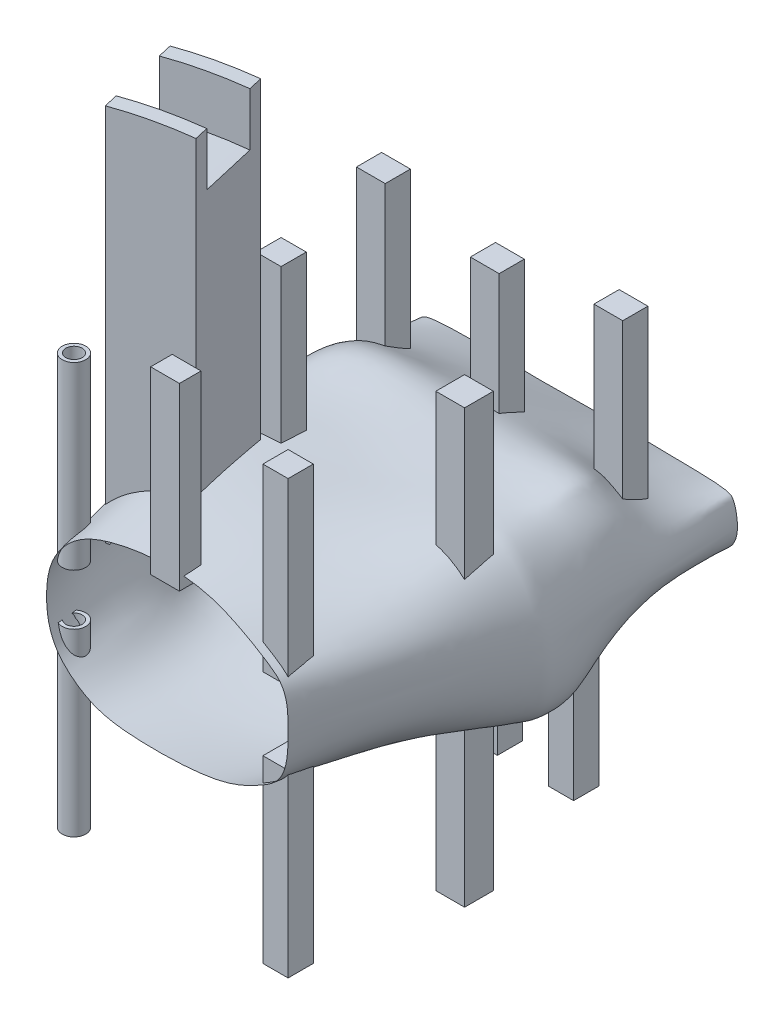
SolidWorks part; units mm, degrees
ref_plane "Front Plane" through (0, 0, 0) normal (0, 0, 1) x (1, 0, 0)
ref_plane "Top Plane" through (0, 0, 0) normal (0, 1, 0) x (1, 0, 0)
ref_plane "Right Plane" through (0, 0, 0) normal (1, 0, 0) x (0, 0, -1)
sketch "Sketch1" plane through (0, 8, 0) normal (0, 1, 0) x (1, 0, 0)
  line L1 (-4, -2.5) -> (4, -2.5)
  line L2 (-4, -2.5) -> (-4, -9.5)
  line L3 (-4, -9.5) -> (4, -9.5)
  line L4 (4, -2.5) -> (4, -9.5)
  line L5 (62, -2.5) -> (70, -2.5)
  line L6 (62, -2.5) -> (62, -9.5)
  line L7 (62, -9.5) -> (70, -9.5)
  line L8 (70, -2.5) -> (70, -9.5)
extrude "Boss-Extrude1" add sketch "Sketch1" along normal blind 50 from offset 0.1
sketch "Sketch2" plane through (0, 4, 0) normal (0, 1, 0) x (1, 0, 0)
  line L10 (37.5, -11.35) -> (37.5, -4.35)
  line L11 (37.5, -4.35) -> (29.5, -4.35)
  line L12 (29.5, -4.35) -> (29.5, -11.35)
  line L13 (29.5, -11.35) -> (33.75, -11.35)
  line L14 (33.75, -11.35) -> (37.5, -11.35)
  line L15 (37.5, -11.35) -> (37.5, -4.35)
  line L16 (37.5, -4.35) -> (29.5, -4.35)
  line L17 (29.5, -4.35) -> (29.5, -11.35)
  line L18 (29.5, -11.35) -> (33.75, -11.35)
  line L19 (33.75, -11.35) -> (37.5, -11.35)
  dimension "D1" = 0.2
extrude "Boss-Extrude2" add sketch "Sketch2" along normal blind 50 from offset 0.1 separate body
sketch "Sketch3" plane through (0, 9, 0) normal (0, 1, 0) x (1, 0, 0)
  line L1 (-9.75, -44.95) -> (-2.75, -44.95)
  line L2 (-9.75, -44.95) -> (-9.75, -51.95)
  line L3 (-9.75, -51.95) -> (-2.75, -51.95)
  line L4 (-2.75, -44.95) -> (-2.75, -51.95)
extrude "Boss-Extrude3" add sketch "Sketch3" along normal blind 50 from offset 0.1 separate body
sketch "Sketch4" plane through (0, 16, 0) normal (0, 1, 0) x (1, 0, 0)
  line L4 (17.5, -51.95) -> (17.5, -44.95)
  line L5 (17.5, -44.95) -> (10.5, -44.95)
  line L6 (10.5, -44.95) -> (10.5, -51.95)
  line L7 (10.5, -51.95) -> (17.5, -51.95)
  line L8 (17.5, -51.95) -> (17.5, -44.95)
  line L9 (17.5, -44.95) -> (10.5, -44.95)
  line L10 (10.5, -44.95) -> (10.5, -51.95)
  line L11 (10.5, -51.95) -> (17.5, -51.95)
  dimension "D1" = 0
extrude "Boss-Extrude4" add sketch "Sketch4" along normal blind 50 from offset 0.1 separate body
sketch "Sketch5" plane through (0, 8, 0) normal (0, 1, 0) x (1, 0, 0)
  line L4 (61, -52.45) -> (69, -52.45)
  line L5 (69, -52.45) -> (69, -44.45)
  line L6 (69, -44.45) -> (61, -44.45)
  line L7 (61, -44.45) -> (61, -52.45)
  line L8 (61, -52.45) -> (69, -52.45)
  line L9 (69, -52.45) -> (69, -44.45)
  line L10 (69, -44.45) -> (61, -44.45)
  line L11 (61, -44.45) -> (61, -52.45)
  dimension "D1" = 0
extrude "Boss-Extrude5" add sketch "Sketch5" along normal blind 50 from offset 0.1 separate body
sketch "Sketch6" plane through (0, 9, 0) normal (0, 1, 0) x (1, 0, 0)
  line L4 (55.5, -95) -> (62.5, -95)
  line L5 (62.5, -95) -> (62.5, -88)
  line L6 (62.5, -88) -> (55.5, -88)
  line L7 (55.5, -88) -> (55.5, -95)
  line L8 (55.5, -95) -> (62.5, -95)
  line L9 (62.5, -95) -> (62.5, -88)
  line L10 (62.5, -88) -> (55.5, -88)
  line L11 (55.5, -88) -> (55.5, -95)
  dimension "D1" = 0
extrude "Boss-Extrude6" add sketch "Sketch6" along normal blind 50 from offset 0.1 separate body
sketch "Sketch7" plane through (0, 20, 0) normal (0, 1, 0) x (1, 0, 0)
  line L8 (35.5, -92.2) -> (27.5, -92.2)
  line L9 (27.5, -92.2) -> (27.5, -98.2)
  line L10 (27.5, -98.2) -> (35.5, -98.2)
  line L11 (35.5, -98.2) -> (35.5, -92.2)
  line L12 (35.5, -92.2) -> (27.5, -92.2)
  line L13 (27.5, -92.2) -> (27.5, -98.2)
  line L14 (27.5, -98.2) -> (35.5, -98.2)
  line L15 (35.5, -98.2) -> (35.5, -92.2)
  dimension "D1" = 0.2
extrude "Boss-Extrude7" add sketch "Sketch7" along normal blind 50 from offset 0.1 separate body
sketch "Sketch8" plane through (0, 6, 0) normal (0, 1, 0) x (1, 0, 0)
  circle A0 centre (-0.5, -91.5) radius 2.275
  circle A1 centre (-0.5, -91.5) radius 3.275
  arc A2 (-1.6902, -94.5511) -> (-1.0727, -88.2755) centre (-0.5, -91.5) ccw construction
  circle A3 centre (-0.5, -91.5) radius 2.275 construction
extrude "Boss-Extrude8" add sketch "Sketch8" along normal blind 50 from offset 0.1 separate body
sketch "Sketch9" plane through (0, -12, 0) normal (0, -1, 0) x (1, 0, 0)
  line L1 (7.5, 11.65) -> (14.5, 11.65)
  line L2 (7.5, 11.65) -> (7.5, 4.65)
  line L3 (7.5, 4.65) -> (14.5, 4.65)
  line L4 (14.5, 11.65) -> (14.5, 4.65)
  line L5 (30, 11.35) -> (37, 11.35)
  line L6 (30, 11.35) -> (30, 4.35)
  line L7 (30, 4.35) -> (37, 4.35)
  line L8 (37, 11.35) -> (37, 4.35)
  line L9 (58.5, 11.65) -> (51.5, 11.65)
  line L10 (58.5, 11.65) -> (58.5, 4.65)
  line L11 (58.5, 4.65) -> (51.5, 4.65)
  line L12 (51.5, 11.65) -> (51.5, 4.65)
  line L13 (61, 52.45) -> (69, 52.45)
  line L14 (61, 52.45) -> (61, 44.45)
  line L15 (61, 44.45) -> (69, 44.45)
  line L16 (69, 52.45) -> (69, 44.45)
extrude "Boss-Extrude9" add sketch "Sketch9" along normal blind 50 from offset 0.1 separate body
sketch "Sketch10" plane through (0, -11, 0) normal (0, -1, 0) x (1, 0, 0)
  line L1 (55.5, 95) -> (62.5, 95)
  line L2 (55.5, 95) -> (55.5, 88)
  line L3 (55.5, 88) -> (62.5, 88)
  line L4 (62.5, 95) -> (62.5, 88)
  line L5 (17.5, 51.95) -> (10.5, 51.95)
  line L6 (17.5, 51.95) -> (17.5, 44.95)
  line L7 (17.5, 44.95) -> (10.5, 44.95)
  line L8 (10.5, 51.95) -> (10.5, 44.95)
extrude "Boss-Extrude10" add sketch "Sketch10" along normal blind 50 from offset 0.1 separate body
sketch "Sketch11" plane through (0, -8, 0) normal (0, -1, 0) x (1, 0, 0)
  circle A0 centre (-0.5, 91.5) radius 2.275 construction
  circle A1 centre (-0.5, 91.5) radius 3.275
  circle A2 centre (-0.5, 91.5) radius 3.275
  circle A3 centre (-0.5, 91.5) radius 2.275
  dimension "D1" = 0
extrude "Boss-Extrude11" add sketch "Sketch11" along normal blind 50 from offset 0.1 separate body
ref_plane "Plane1" through (12.8977, 0, 55.8661) normal (0.225, 0, 0.9744) x (0.9744, 0, -0.225)
ref_plane "Plane2" through (15.1472, 0, 65.6098) normal (0.225, 0, 0.9744) x (0.9744, 0, -0.225)
sketch "Sketch12" plane through (12.8977, 0, 55.8661) normal (0.225, 0, 0.9744) x (0.9744, 0, -0.225)
  circle A0 centre (-9.3704, 0) radius 10.7
  dimension "D1" = 21.4
extrude "Extrude-Thin1" add sketch "Sketch12" along normal mid plane 4 separate body thin thin type one direction wall 100
sketch "Sketch13" plane through (13.3476, 0, 57.8148) normal (0.225, 0, 0.9744) x (0.9744, 0, -0.225)
  line L0 (0.0896, 5) -> (1.1296, 5)
  line L1 (1.1296, 5) -> (1.1296, 110.2009)
  line L2 (-19.8704, 110.2009) -> (-19.8704, 5)
  line L3 (-20.0704, 6) -> (-20.0704, 0) construction
  line L4 (1.3296, 6) -> (1.3296, 0) construction
  line L5 (-19.8704, 5) -> (-18.8303, 5)
  line L6 (-15.9888, 6) -> (-22.9251, 6) construction
  circle A0 centre (-9.3704, 0) radius 10.7 construction
  circle A1 centre (-9.3704, 0) radius 110.7 construction
  arc A2 (-19.8704, 110.2009) -> (1.1296, 110.2009) centre (-9.3704, 0) ccw
  arc A3 (0.0896, 5) -> (-18.8303, 5) centre (-9.3704, 0) ccw
  dimension "D1" = 0.2
  dimension "D2" = 0.2
  dimension "D3" = 1
extrude "Cut-Extrude1" cut sketch "Sketch13" against normal through all both and the other way through all
mirror "Mirror1" about plane through (15.1472, 0, 65.6098) normal (0.225, 0, 0.9744) of bodies 118
sketch "Sketch14" plane through (17.8466, 0, 77.3022) normal (0.225, 0, 0.9744) x (0.9744, 0, -0.225)
  circle A0 centre (-9.3704, 0) radius 16
  dimension "D1" = 32
extrude "Extrude-Thin2" add sketch "Sketch14" against normal up to surface (24 mm away) thin up to face at (3.3176, 41.1002, 56.0252) thin type one direction wall 80
extrude "Cut-Extrude2" cut sketch "Sketch13<3>" against normal through all both and the other way through all
sketch "Sketch13<3>" plane through (13.3476, 0, 57.8148) normal (0.225, 0, 0.9744) x (0.9744, 0, -0.225) same geometry as "Sketch13"
fillet "Fillet1" radius 0.5 2 edges at (16.2479, 12.0727, 65.3557) (-4.2139, 12.0727, 70.0796)
ref_plane "Plane3" through (0, 0, 0) normal (0, 1, 0) x (1, 0, 0)
sketch "Sketch15" plane through (0, 0, 0) normal (0, 1, 0) x (1, 0, 0)
  line L0 (-12.1525, 15) -> (-15.2953, -40.3087)
  line L1 (-15.0551, -43.1255) -> (-2.294, -98.4)
  line L2 (64.1595, -98.4) -> (79.2818, -41.9628)
  line L3 (79.614, -38.9613) -> (77.3822, 15)
  line L4 (76.3839, -33.4595) -> (75, 0) construction
  line L5 (76.7992, -43.5006) -> (63.0268, -94.9) construction
  line L6 (-12.3568, -41.4768) -> (-8.5998, -57.7502) construction
  line L7 (-10, 0) -> (-12.2621, -39.8092) construction
  line L9 (64.1595, -98.4) -> (65.0973, -94.9)
  line L10 (-2.294, -98.4) -> (-3.102, -94.9)
  line L12 (75, 0) -> (47, 0) construction
  arc A0 (79.2818, -41.9628) -> (79.614, -38.9613) centre (69.6226, -39.3746) ccw
  arc A1 (-15.2953, -40.3087) -> (-15.0551, -43.1255) centre (-5.3114, -40.876) ccw
  point P14 (0, 0)
  point P24 (0, 0)
  point P25 (63.9468, -99.1937)
  point P26 (0, 0)
  point P28 (0, 0)
  point P30 (0, 0)
  point P32 (0, 0)
  point P33 (-11.5291, 25.9717)
  point P34 (0, 0)
  point P35 (77.212, 19.1146)
  point P36 (77.0804, 22.2963)
  dimension "D5" = 10
  dimension "D1" = 3
  dimension "D2" = 2
  dimension "D3" = 3
  dimension "D4" = 3
  dimension "D6" = 15
ref_plane "Plane4" through (0, 0, -15) normal (0, 0, -1) x (-1, 0, 0)
ref_plane "Plane5" through (0, 0, 41.97) normal (0, 0, 1) x (1, 0, 0)
ref_plane "Plane6" through (0, 0, 29.03) normal (0, 0, -1) x (-1, 0, 0)
ref_plane "Plane7" through (0, 0, 67.45) normal (0, 0, 1) x (1, 0, 0)
ref_plane "Plane8" through (0, 0, 97) normal (0, 0, 1) x (1, 0, 0)
sketch "Sketch16" plane through (0, 0, -15) normal (0, 0, -1) x (-1, 0, 0)
  line L0 (-64.1595, 0) -> (-79.2818, 0) construction
  line L1 (-79.614, 0) -> (-77.3822, 0) construction
  line L2 (15.0551, 0) -> (2.294, 0) construction
  spline S0 degree 3 poles (-71.1852, -9.0827) (-78.6693, -4.8815) (-76.8048, 5.1779) (-74.9375, 7.6273) (-44.2299, 7.9457) (-51.3054, 8.2091) (-16.6288, 7.6603) (-20.5035, 8.0278) (8.9045, 8.0076) (11.3889, 5.5481) (12.2889, 1.7755) (11.9298, -3.3745) (11.1196, -8.9657) (-11.6903, -7.8226) (-16.6557, -9.5364) (-48.9186, -8.3026) (-56.5707, -7.9846) (-71.1852, -9.0827) (-78.6693, -4.8815) (-76.8048, 5.1779) knots -0.231953 -0.094003 -0.053059 0 0.019528 0.023803 0.04275 0.118919 0.206181 0.302051 0.336436 0.343183 0.366589 0.374014 0.414502 0.467056 0.636571 0.768047 0.905997 0.946941 1 1.019528 1.023803 1.04275 only from (-77.3822, 0) to (-77.3822, 0)
  point P2 (-75.5767, 6.9122)
  point P4 (-75.1062, -8.6557)
  point P6 (-69.5004, 9.0908)
  point P8 (-75.1149, 6.9745)
  point P10 (-74.5535, -8.0983)
  point P12 (-66.4034, 8.5614)
  point P14 (-46.5361, 8.2128)
  point P16 (-64.2424, 8.0386)
  point P18 (-46.2922, 7.8991)
  point P20 (-24.0813, 7.8368)
  point P22 (-5.1953, 8.0021)
  point P24 (10.798, 5.7457)
  point P26 (10.5557, 6.1817)
  point P27 (0, 0)
  point P34 (-65.2276, -9.6842)
  point P35 (-73.9069, -8.1232)
  point P37 (10.6701, -7.0069)
  point P38 (-63.0421, -8.4978)
  point P39 (-45.3088, -8.4354)
  point P40 (-24.1411, -9.1222)
  point P41 (1.441, -8.5356)
  point P42 (-23.1641, -8.4925)
  point P43 (-22.8662, -8.9897)
  point P44 (-0.6234, -8.4463)
  point P45 (9.8283, -7.237)
  point P46 (10.3898, 6.497)
  point P47 (0, 0)
  point P49 (-70.4738, -8.281)
  point P50 (-75.8251, 6.4125)
  point P51 (-44.7505, 8.0667)
  point P52 (-63.2214, 7.7557)
ref_plane "Plane9" through (0, 0, 6) normal (0, 0, -1) x (-1, 0, 0)
ref_plane "Plane10" through (0, 0, 14.03) normal (0, 0, -1) x (-1, 0, 0)
sketch "Sketch17" plane through (0, 0, 6) normal (0, 0, -1) x (-1, 0, 0)
  spline S0 degree 3 poles (-68.0119, -15.5416) (-80.9408, -1.0869) (-73.7901, 13.4909) (-57.3873, 17.4575) (-36.356, 18.2513) (-14.0029, 18.309) (9.8666, 15.5883) (14.5902, 0.3253) (10.1134, -10.7393) (-5.7392, -14.2522) (-24.5288, -13.8354) (-47.1281, -13.9771) (-68.0119, -15.5416) (-80.9408, -1.0869) (-73.7901, 13.4909) knots -0.279953 -0.1735 -0.064737 0 0.053921 0.129971 0.224347 0.351478 0.461867 0.510928 0.554879 0.613872 0.720047 0.8265 0.935263 1 1.053921 1.129971 1.224347 only from (-78.2507, 0) to (-78.2507, 0)
  point P2 (0, 0)
  point P4 (10.3011, 8.9171)
  point P6 (9.6866, -8.5937)
  point P8 (0, 0)
  point P10 (9.9938, -8.3743)
  point P12 (-4.6643, -12.9824)
  point P14 (-24.5041, -14.2451)
  point P16 (-47.191, -14.2471)
  point P18 (-70.0862, -11.073)
  point P20 (-73.7806, 9.3245)
  point P22 (-59.1069, 15.5686)
  point P23 (-11.8304, 16.4321)
  point P26 (-24.57, -13.9405)
  point P27 (-2.0228, -13.0733)
  point P28 (-73.7888, 10.5548)
  point P29 (-58.8097, 16.624)
  point P30 (-38.805, 18.0637)
  point P31 (-11.7907, 17.6541)
  point P32 (10.384, 9.9969)
sketch "Sketch18" plane through (0, 0, 14.03) normal (0, 0, -1) x (-1, 0, 0)
  spline S0 degree 3 poles (-78.1744, -5.7209) (-78.8867, 3.3384) (-75.8875, 10.8583) (-72.3342, 15.9421) (-69.0351, 18.3111) (-64.1979, 22.009) (-39.0825, 20.8471) (-20.663, 22.2437) (4.4452, 22.3694) (16.2899, 4.0467) (11.6003, -19.0656) (-3.4549, -17.7642) (-24.9715, -18.5851) (-44.1357, -17.5762) (-72.3303, -16.6356) (-78.1744, -5.7209) (-78.8867, 3.3384) (-75.8875, 10.8583) knots -0.173726 -0.091095 -0.009109 0 0.068298 0.084008 0.148983 0.166724 0.253293 0.360225 0.438075 0.532552 0.595553 0.656082 0.718049 0.826274 0.908905 0.990891 1 1.068298 1.084008 1.148983 only from (-78.5829, 0) to (-78.5829, 0)
  point P2 (0, 0)
  point P4 (-66.8285, 20.2511)
  point P6 (-42.5875, 21.6094)
  point P8 (0, 0)
  point P10 (-74.0903, 13.4072)
  point P12 (-17.3256, 22.1027)
  point P14 (1.5583, 19.6078)
  point P16 (-66.966, 19.8659)
  point P18 (-43.4793, 21.3715)
  point P20 (0, 0)
  point P22 (7.6781, -13.0552)
  point P23 (-19.9094, -16.5923)
  point P26 (-4.3134, -15.5113)
  point P27 (-20.1024, -15.3183)
  point P28 (-4.5837, -15.2025)
  point P29 (7.924, -12.1914)
  point P30 (-46.7061, -15.7012)
  point P31 (-68.097, -14.8419)
  point P32 (-3.7064, -14.8738)
  point P33 (-69.5062, -14.1704)
  point P34 (9.3546, -14.6553)
  point P35 (-3.7101, -16.9519)
  point P36 (-20.0241, -16.973)
  point P37 (9.6305, -15.6958)
  point P38 (-3.7001, -18.0905)
  point P39 (-20.2636, -18.2502)
  point P40 (-47.7655, -17.5074)
sketch "Sketch19" plane through (0, 0, 29.03) normal (0, 0, -1) x (-1, 0, 0)
  spline S0 degree 3 poles (-79.171, -20.3631) (-80.7638, -0.0393) (-75.5328, 14.2924) (-67.5362, 20.7237) (-56.7767, 23.0714) (-38.5157, 22.4921) (-17.4291, 23.1266) (5.9183, 21.7112) (17.2856, 2.3447) (13.4244, -11.838) (9.5174, -21.2535) (0.1006, -21.5099) (-11.9829, -21.6909) (-28.8316, -21.4847) (-47.7412, -21.657) (-62.671, -22.9052) (-79.171, -20.3631) (-80.7638, -0.0393) (-75.5328, 14.2924) knots -0.191554 -0.118168 -0.086598 0 0.071895 0.105684 0.119135 0.2064 0.329313 0.384742 0.484271 0.550555 0.566403 0.603602 0.648592 0.724046 0.808446 0.881832 0.913402 1 1.071895 1.105684 1.119135 only from (-79.2033, 0) to (-79.2033, 0)
  point P2 (0, 0)
  point P4 (1.138, -20.0455)
  point P6 (-10.409, -21.1383)
  point P8 (0, 0)
  point P10 (9.516, -20.1184)
  point P12 (11.738, -15.8201)
  point P14 (0, 0)
  point P16 (9.9167, -19.2077)
  point P18 (1.138, -20.7376)
  point P20 (0, 0)
  point P22 (-28.0538, -21.5558)
  point P24 (-48.5336, -21.9294)
  point P26 (-66.3422, -22.1617)
  point P28 (-72.6139, -20.6131)
  point P29 (-9.7418, -21.6197)
  point P32 (1.1756, -21.4648)
  point P33 (-73.7753, -20.3034)
  point P34 (0, 0)
  point P35 (-72.5439, 16.1274)
  point P36 (-64.9898, 21.2221)
  point P37 (-11.6791, 22.6539)
  point P38 (1.5657, 20.3012)
sketch "Sketch20" plane through (0, 0, 41.97) normal (0, 0, 1) x (1, 0, 0)
  spline S0 degree 3 poles (-13.7918, -14.018) (-17.4972, -1.0196) (-11.9374, 10.2837) (-5.1797, 19.1082) (3.1572, 22.1096) (21.6152, 23.5732) (39.0515, 22.136) (57.9967, 23.4248) (70.1604, 19.6682) (76.8965, 11.3257) (80.3663, -2.3328) (79.808, -20.8805) (61.4518, -21.9017) (46.2737, -22.2041) (26.9211, -21.9961) (11.4125, -21.526) (-0.0103, -21.683) (-7.9367, -21.8247) (-13.7918, -14.018) (-17.4972, -1.0196) (-11.9374, 10.2837) knots -0.121971 -0.087846 -0.075649 0 0.058041 0.072558 0.137106 0.15903 0.283733 0.368469 0.38409 0.439936 0.484587 0.568827 0.605034 0.689826 0.764361 0.842217 0.878029 0.912154 0.924351 1 1.058041 1.072558 1.137106 only from (-15.2514, 0) to (-15.2514, 0)
  spline S1 degree 3 poles (79.171, -20.3631) (80.7638, -0.0393) (75.5328, 14.2924) (67.5362, 20.7237) (56.7767, 23.0714) (38.5157, 22.4921) (17.4291, 23.1266) (-5.9183, 21.7112) (-17.2856, 2.3447) (-13.4244, -11.838) (-9.5174, -21.2535) (-0.1006, -21.5099) (11.9829, -21.6909) (28.8316, -21.4847) (47.7412, -21.657) (62.671, -22.9052) (79.171, -20.3631) (80.7638, -0.0393) (75.5328, 14.2924) knots -0.191554 -0.118168 -0.086598 0 0.071895 0.105684 0.119135 0.2064 0.329313 0.384742 0.484271 0.550555 0.566403 0.603602 0.648592 0.724046 0.808446 0.881832 0.913402 1 1.071895 1.105684 1.119135 only from (79.2033, 0) to (79.2033, 0) construction
  point P2 (0, 0)
  point P4 (0, 0)
  point P6 (45.2983, -22.1106)
  point P8 (0, 0)
  point P10 (74.5754, -19.9509)
  point P12 (0, 0)
  point P14 (27.1625, -21.9399)
  point P16 (8.3977, -22.0537)
  point P18 (-5.7984, -20.8555)
  point P20 (-9.7922, -19.8753)
  point P22 (-0.4931, -21.6969)
  point P24 (-9.4832, -19.6228)
  point P27 (8.2207, -21.6108)
  point P30 (76.3285, 10.4565)
  point P31 (65.5625, 21.0431)
  point P32 (42.7181, 22.7741)
  point P33 (9.0033, 22.5386)
  point P34 (-8.825, 14.3161)
sketch "Sketch21" plane through (0, 0, 67.45) normal (0, 0, 1) x (1, 0, 0)
  spline S0 degree 3 poles (72.0226, -9.858) (72.6835, -0.2396) (71.9233, 9.6159) (61.9224, 19.1374) (43.786, 23.8713) (29.8096, 24.6807) (11.4977, 23.7767) (1.1455, 20.6848) (-9.0886, 10.6402) (-10.4839, -2.3394) (-4.23, -12.4476) (6.095, -20.6415) (24.7956, -24.2725) (42.7476, -24.5128) (58.4196, -21.637) (65.3855, -16.9346) (72.0226, -9.858) (72.6835, -0.2396) (71.9233, 9.6159) knots -0.130522 -0.090139 -0.044745 0 0.041447 0.0902 0.182445 0.293673 0.315758 0.403301 0.458698 0.503428 0.577284 0.614864 0.687699 0.838111 0.869478 0.909861 0.955255 1 1.041447 1.0902 1.182445 only from (72.4526, 0) to (72.4526, 0)
  point P2 (0, 0)
  point P4 (69.7591, 18.7365)
  point P6 (64.0184, 16.3042)
  point P8 (71.0278, 8.6854)
  point P10 (0, 0)
  point P12 (20.125, 21.3824)
  point P14 (0, 0)
  point P16 (-0.4315, 18.2175)
  point P18 (0, 0)
  point P20 (46.2746, 21.8493)
  point P22 (71.008, -9.3912)
  point P24 (64.9237, -16.8682)
  point P26 (57.6316, -21.3808)
  point P28 (49.4493, -22.5497)
  point P29 (19.0107, -22.6843)
  point P30 (18.4436, -23.3402)
  point P31 (-8.2447, 9.4233)
  point P33 (4.6489, -20.4176)
  point P34 (0, 0)
  point P35 (-11.7223, 9.9754)
  point P36 (4.32, -18.6831)
  point P38 (-1.9948, -13.8039)
  point P39 (19.2052, -22.8842)
  point P40 (51.1457, -22.8966)
  point P41 (20.2924, 22.3816)
  point P42 (0, 0)
  point P43 (19.5313, 23.4501)
  point P44 (45.5667, 22.8802)
  point P45 (19.3536, 24.1502)
sketch "Sketch23" plane through (0, 0, 97) normal (0, 0, 1) x (1, 0, 0)
  spline S0 degree 3 poles (-1.7622, -11.0322) (-3.0627, -1.2714) (-1.7373, 8.928) (5.1339, 17.869) (16.785, 21.9242) (28.6762, 23.6082) (38.7998, 23.1123) (46.7462, 20.695) (53.1142, 17.4728) (58.1841, 14.5114) (64.4308, 9.872) (64.6852, -0.596) (64.1983, -12.1853) (56.235, -16.9491) (47.9884, -21.1109) (35.7099, -22.7051) (22.7771, -22.749) (12.3318, -21.6135) (4.9204, -17.5797) (-1.7622, -11.0322) (-3.0627, -1.2714) (-1.7373, 8.928) knots -0.146785 -0.109783 -0.0633 0 0.04164 0.103384 0.171354 0.237511 0.299646 0.334713 0.372416 0.415626 0.431444 0.496386 0.569876 0.603538 0.640162 0.721933 0.800387 0.853215 0.890217 0.9367 1 1.04164 1.103384 1.171354 only from (-2.6172, 0) to (-2.6172, 0)
  point P2 (5.454, 16.6191)
  point P4 (40.3554, 22.439)
  point P6 (52.768, 17.576)
  point P8 (0, 0)
  point P10 (0, 0)
  point P12 (56.4177, -16.758)
  point P14 (-0.7988, 10.0871)
  point P16 (0, 0)
  point P18 (0, 0)
  point P20 (61.8045, 11.6161)
  point P22 (-0.2696, -11.3916)
  point P24 (-1.358, 7.5467)
surface "Surface-Loft1"
